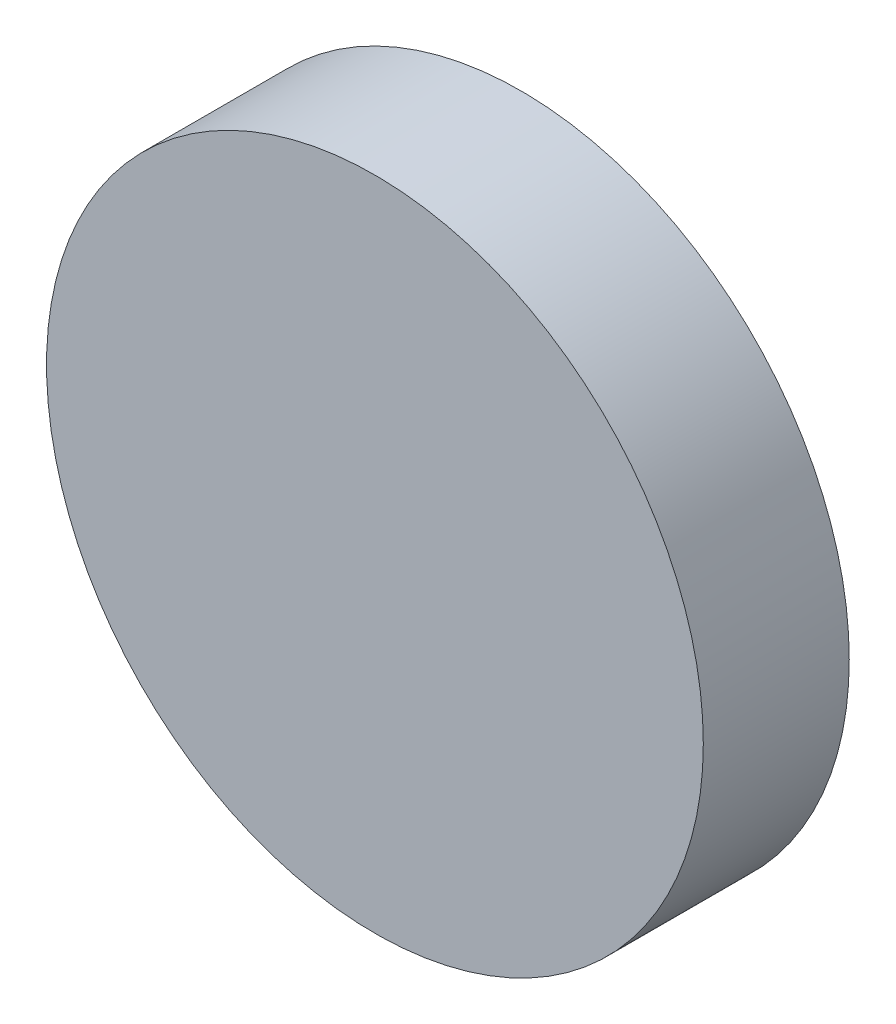
SolidWorks part; units mm, degrees
ref_plane "Front Plane" through (0, 0, 0) normal (0, 0, 1) x (1, 0, 0)
ref_plane "Top Plane" through (0, 0, 0) normal (0, 1, 0) x (1, 0, 0)
ref_plane "Right Plane" through (0, 0, 0) normal (1, 0, 0) x (0, 0, -1)
sketch "Sketch1" plane through (0, 0, 0) normal (0, 0, 1) x (1, 0, 0)
  circle A0 centre (0, 0) radius 25.15
  circle A1 centre (0, 0) radius 27
  dimension "D1" = 50.3
  dimension "D2" = 54
extrude "Boss-Extrude1" add sketch "Sketch1" along normal blind 10
sketch "Sketch2" plane through (0, 0, 10) normal (0, 0, 1) x (1, 0, 0)
  circle A0 centre (0, 0) radius 27
  circle A1 centre (0, 0) radius 27 construction
  point P8 (0, 0)
  circle M3 centre (0, 0) radius 27
  circle M4 centre (0, 0) radius 25.15
extrude "Boss-Extrude3" add sketch "Sketch2" along normal blind 2 contours M3 M4 | M4 region at (-26.2363, 0, 10) region at (0, 0, 10)
